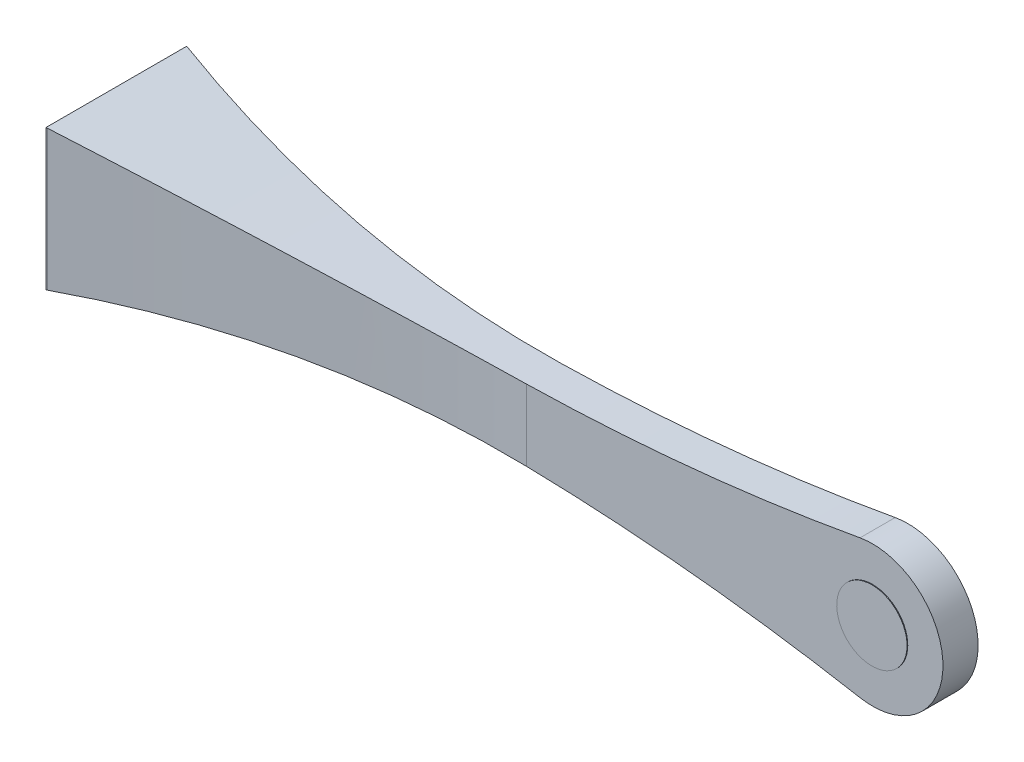
SolidWorks part; units mm, degrees
note: The reader was unsure of these and kept them because the rebuilt part matched: shared geometry of "Sketch1<3>", "Sketch2<2>".
material "Custom Plastic"
ref_plane "Front Plane" through (0, 0, 0) normal (0, 0, 1) x (1, 0, 0)
ref_plane "Top Plane" through (0, 0, 0) normal (0, 1, 0) x (1, 0, 0)
ref_plane "Right Plane" through (0, 0, 0) normal (1, 0, 0) x (0, 0, -1)
sketch "Sketch1" plane through (0, 0, 0) normal (0, 1, 0) x (1, 0, 0)
  line L0 (0, 0) -> (-110, 0) construction
  line L1 (-110, 10) -> (-110, -10)
  line L2 (-55.4545, 5) -> (-110, 5) construction
  circle A0 centre (0, 0) radius 5
  arc A1 (-1.7887, 9.8387) -> (-1.7887, -9.8387) centre (0, 0) cw
  arc A2 (-1.7887, 9.8387) -> (-110, 10) centre (-55.4545, 305.0207) cw
  arc A3 (-1.7887, -9.8387) -> (-110, -10) centre (-55.4545, -305.0207) ccw
  point P13 (-110, 0)
  dimension "D1" = 5
  dimension "D2" = 10
  dimension "D3" = 5
  dimension "D4" = 110
  dimension "D5" = 20
  dimension "D6" = 120
extrude "Boss-Extrude1" add sketch "Sketch1" along normal mid plane 5
extrude "Boss-Extrude2" add sketch "Sketch1<3>" along normal offset from surface 0.1 and the other way offset from surface (2.6 mm away) 0.1 contours A0 up to face at (-52.9508, 2.5, 0) offset beyond the face yes other way up to face at (-52.9508, -2.5, 0)
sketch "Sketch1<3>" plane through (0, 0, 0) normal (0, 1, 0) x (1, 0, 0) same geometry as "Sketch1"
sketch "Sketch2" plane through (-110, 0, 0) normal (-1, 0, 0) x (0, 0, 1)
  line L5 (10, 2.5) -> (10, -2.5) construction
  line L6 (-10, -10) -> (10, -10)
  line L7 (-10, -10) -> (-10, 10)
  line L8 (-10, 10) -> (10, 10)
  line L9 (10, -10) -> (10, 10)
  line L10 (-10, -10) -> (10, 10) construction
  line L11 (-10, 10) -> (10, -10) construction
  point P0 (0, 0)
  dimension "D1" = 20
  dimension "D2" = 20
extrude "Boss-Extrude3" add sketch "Sketch2" along normal blind 10
chamfer "Chamfer1" distance 30 distance2 7.5 1 edges at (-110, -2.5, 0)
chamfer "Chamfer2" distance 7.5 distance2 30 1 edges at (-110, 2.5, 0)
extrude "Cut-Extrude1" cut sketch "Sketch2<2>" along normal through all
sketch "Sketch2<2>" plane through (-110, 0, 0) normal (-1, 0, 0) x (0, 0, 1) same geometry as "Sketch2"
fillet "Fillet1" radius 250 2 edges at (-80, 2.5, 0) (-80, -2.5, 0)
move or copy body "Body-Move/Copy1" bodies to move or copy 105 copy no rotation origin (0, 0, 0) rotation axis (1, 0, 0) rotation angle 90
